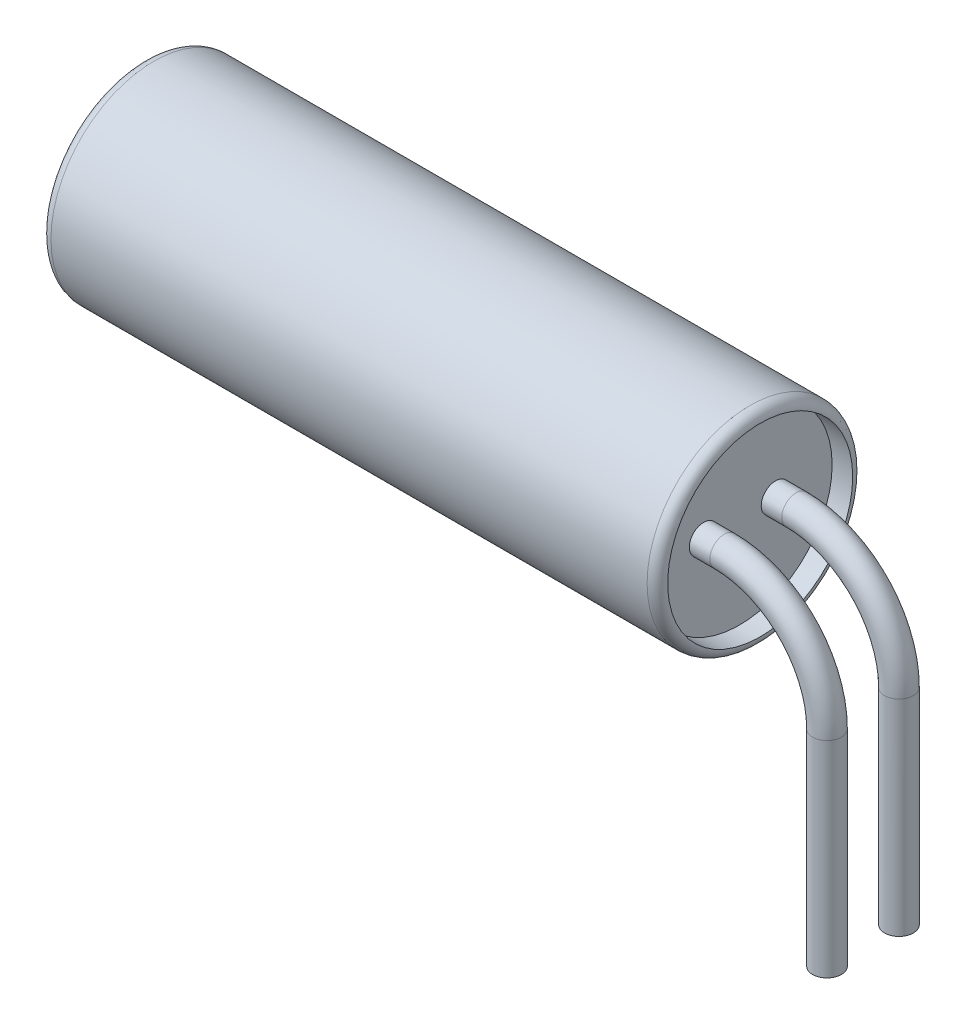
SolidWorks part; units mm, degrees
ref_plane "前视基准面" through (0, 0, 0) normal (0, 0, 1) x (1, 0, 0)
ref_plane "上视基准面" through (0, 0, 0) normal (0, 1, 0) x (1, 0, 0)
ref_plane "右视基准面" through (0, 0, 0) normal (1, 0, 0) x (0, 0, -1)
sketch "草图1" plane through (0, 0, 0) normal (1, 0, 0) x (0, 0, -1)
  circle A0 centre (0, 0) radius 1
extrude "凸台-拉伸1" add sketch "草图1" against normal blind 6
sketch "草图2" plane through (0, 0, 0) normal (1, 0, 0) x (0, 0, -1)
  circle A0 centre (0, 0) radius 0.9
extrude "切除-拉伸1" cut sketch "草图2" against normal blind 5.8
sketch "草图5" plane through (-5.8, 0, 0) normal (1, 0, 0) x (0, 0, -1)
  circle A0 centre (0, 0) radius 0.9
extrude "凸台-拉伸4" add sketch "草图5" along normal blind 5.6 separate body
sketch "草图7" plane through (-0.2, 0, 0) normal (1, 0, 0) x (0, 0, -1)
  circle A0 centre (0.35, 0) radius 0.14
sketch3d "3D草图3"
  line L0 (-0.2, 0, -0.35) -> (0, 0, -0.35)
  line L3 (1, -1, -0.35) -> (1, -3, -0.35)
  arc A0 (0, 0, -0.35) -> (1, -1, -0.35) centre (0, -1, -0.35) ccw
  point P6 (0, -1, -1.35)
  dimension "D1" = 0.35
sweep "扫描1" add profiles "草图7" path "3D草图3"
mirror "镜向1" about plane through (0, 0, 0) normal (0, 0, 1) of "扫描1"
fillet "圆角1" radius 0.1 1 edges at (-6, 0, -1)
fillet "圆角2" radius 0.1 1 edges at (0, 0, -1)
